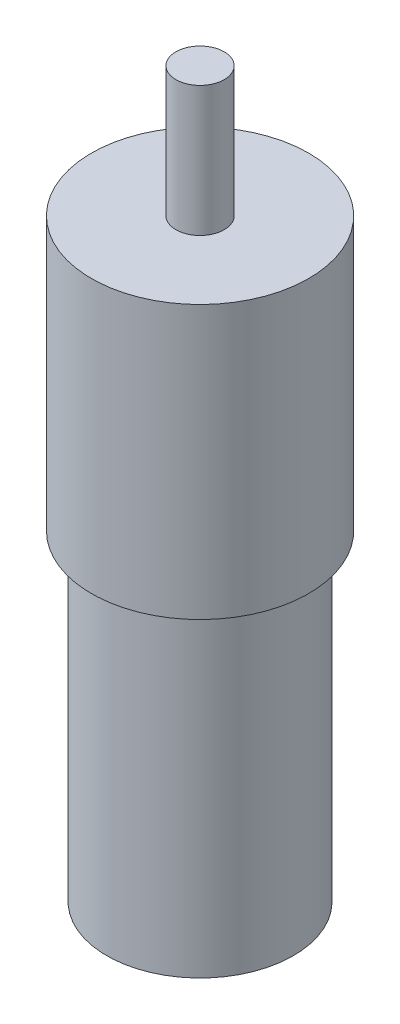
SolidWorks part; units mm, degrees
ref_plane "Front" through (0, 0, 0) normal (0, 0, 1) x (1, 0, 0)
ref_plane "Top" through (0, 0, 0) normal (0, 1, 0) x (1, 0, 0)
ref_plane "Right" through (0, 0, 0) normal (1, 0, 0) x (0, 0, -1)
sketch "Sketch1" plane through (0, 0, 0) normal (0, 1, 0) x (1, 0, 0)
  circle A0 centre (0, 0) radius 22.5044
  dimension "D1" = 45.0088
extrude "Boss-Extrude1" add sketch "Sketch1" along normal blind 56.515
sketch "Sketch2" plane through (0, 56.515, 0) normal (0, 1, 0) x (1, 0, 0)
  circle A0 centre (0, 0) radius 5
  dimension "D1" = 10
extrude "Boss-Extrude2" add sketch "Sketch2" along normal blind 26.924
sketch "Sketch3" plane through (0, 0, 0) normal (0, -1, 0) x (1, 0, 0)
  circle A0 centre (0, 0) radius 19.3294
  circle A1 centre (0, 0) radius 22.5044 construction
  dimension "D1" = 3.175
extrude "Boss-Extrude3" add sketch "Sketch3" along normal blind 66.548
